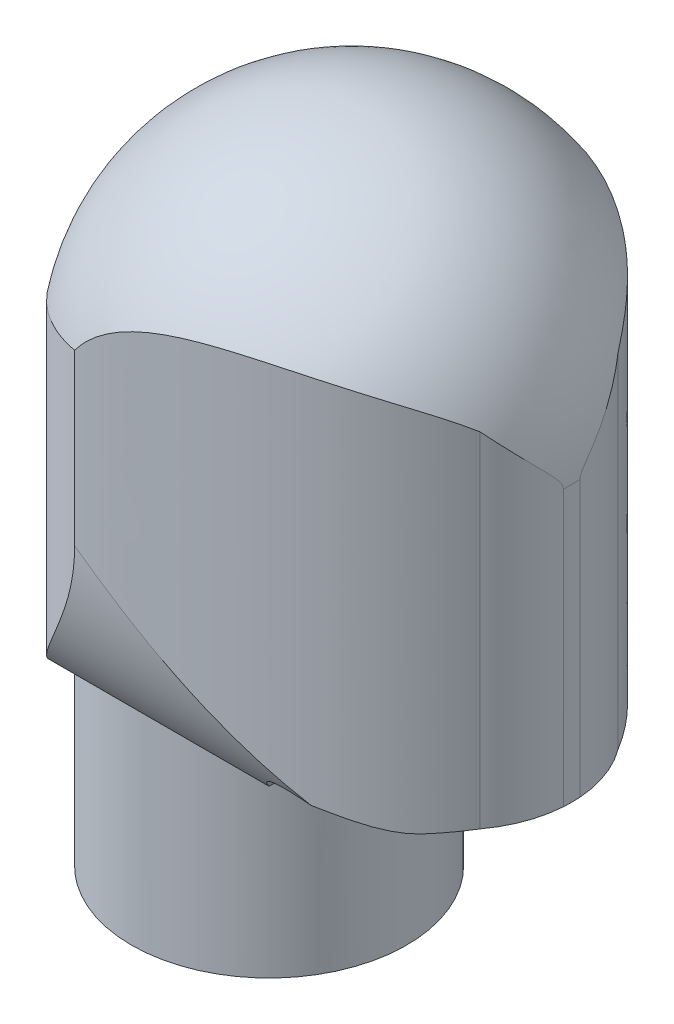
SolidWorks part; units mm, degrees
ref_plane "Front Plane" through (0, 0, 0) normal (0, 0, 1) x (1, 0, 0)
ref_plane "Top Plane" through (0, 0, 0) normal (0, 1, 0) x (1, 0, 0)
ref_plane "Right Plane" through (0, 0, 0) normal (1, 0, 0) x (0, 0, -1)
sketch "Sketch4" plane through (0, 0, 0) normal (0, 1, 0) x (1, 0, 0)
  circle A0 centre (0, 0) radius 50
  dimension "D1" = 100
extrude "Boss-Extrude2" add sketch "Sketch4" along normal blind 75
sketch "Sketch5" plane through (0, 75, 0) normal (0, 1, 0) x (1, 0, 0)
  circle A1 centre (30, 0) radius 80
  point P0 (30, 0)
  dimension "D2" = 160
  dimension "D1" = 30
extrude "Boss-Extrude3" add sketch "Sketch5" along normal blind 100 contours A1
sketch "Sketch11" plane through (0, 0, 0) normal (0, 0, 1) x (1, 0, 0)
  line L0 (-50, 175) -> (30, 175) construction
  line L1 (30, 255) -> (30, 175)
  line L2 (30, 175) -> (-50, 175)
  line L3 (30, 278.4231) -> (30, 141.1862) construction
  arc A0 (-50, 175) -> (30, 255) centre (30, 175) cw
revolve "Revolve1" add sketch "Sketch11" angle 360 about L3
sketch "Sketch12" plane through (0, 75, 0) normal (0, -1, 0) x (1, 0, 0)
  line L0 (-50, 0) -> (110, 0) construction
  line L1 (101.7524, 30.288) -> (101.7524, -38.335) construction
  line L2 (0, 78.4899) -> (0, -88.1251) construction
  circle A0 centre (30, 0) radius 80 construction
  arc A1 (101.7524, -25.0813) -> (101.7524, 25.0813) centre (67.9997, 0) ccw
  arc A2 (0, -70.654) -> (0, 70.654) centre (25.2444, 0) cw
  circle A3 centre (30, 0) radius 80
  spline S0 degree 2 poles (0, 70.654) (73.8652, 70.6147) (101.7524, 25.0813) knots 0 0 0 0.802991 0.802991 0.802991
  spline S1 degree 2 poles (0, -70.654) (73.8652, -70.6147) (101.7524, -25.0813) knots 0 0 0 0.802991 0.802991 0.802991
  point P14 (67.9997, 0)
  circle M7 centre (30, 0) radius 80
  circle M8 centre (0, 0) radius 50
extrude "Cut-Extrude1" cut sketch "Sketch12" against normal blind 177 contours A2 S0 A1 M7 M8 | S1 A2 A1 M8 M7 region at (107.5926, 75, -14.6897) region at (107.5926, 75, 14.6897)
sketch "Sketch13" plane through (0, 0, 0) normal (1, 0, 0) x (0, 0, -1)
  line L0 (70.654, 136.2696) -> (70.654, 75)
  line L1 (70.654, 197.5392) -> (70.654, 75) construction
  line L2 (70.654, 75) -> (50, 75)
  line L3 (0, 284.4544) -> (0, -26.1067) construction
  line L4 (-70.654, 136.2696) -> (-70.654, 75)
  line L5 (-70.654, 75) -> (-50, 75)
  spline S0 degree 2 poles (70.654, 136.2696) (70.6903, 99.5656) (50, 75) knots 0 0 0 0.913942 0.913942 0.913942
  spline S1 degree 2 poles (-70.654, 136.2696) (-70.6903, 99.5656) (-50, 75) knots 0 0 0 0.913942 0.913942 0.913942
extrude "Cut-Extrude2" cut sketch "Sketch13" against normal through all both and the other way through all contours S1 L4 L5 | L0 S0 L2 region at (0, 89.4111, -64.6845) region at (0, 89.4111, 64.6845)
sketch "Sketch14" plane through (0, 0, 0) normal (0, 0, 1) x (1, 0, 0)
  line L0 (50, 75) -> (93.1057, 75)
  line L1 (78.5915, 75) -> (101.7524, 75) construction
  spline S0 degree 3 poles (50, 75) (57.6057, 93.7892) (81.0429, 74.7502) (93.1057, 75) knots 0 0 0 0 1 1 1 1
extrude "Cut-Extrude3" cut sketch "Sketch14" against normal through all both and the other way through all contours S0 L0 region at (66.3897, 78.2233, 0)
sketch "Sketch15" plane through (0, 0, 0) normal (0, 0, 1) x (1, 0, 0)
  line L2 (-50, 0) -> (-34.5084, 0)
  line L3 (-50, 0) -> (50, 0) construction
